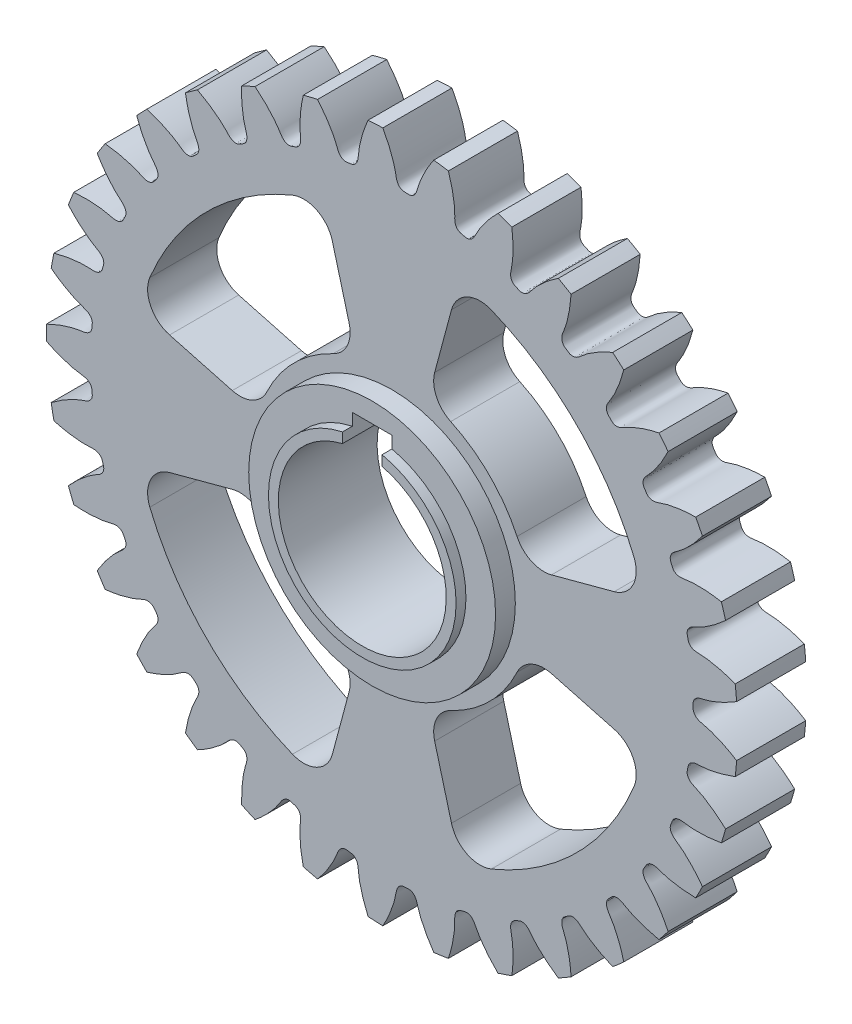
SolidWorks part; units mm, degrees
material "6061 合金"
ref_plane "前视基准面" through (0, 0, 0) normal (0, 0, 1) x (1, 0, 0)
ref_plane "上视基准面" through (0, 0, 0) normal (0, 1, 0) x (1, 0, 0)
ref_plane "右视基准面" through (0, 0, 0) normal (1, 0, 0) x (0, 0, -1)
ref_axis "基准轴1" through (0, 0, 55) along (0, 0, -1)
sketch "旋转草图小直齿轮" plane through (0, 0, 0) normal (1, 0, 0) x (0, 0, -1)
  line L0 (0, 0) -> (1, 0) construction
  line L1 (-10, 0) -> (-10, 35)
  line L2 (-10, 35) -> (10, 35)
  line L3 (10, 35) -> (10, 0)
  line L4 (10, 0) -> (-10, 0)
revolve "小直齿轮" add sketch "旋转草图小直齿轮" angle 360 about L0
sketch "齿草图小直齿轮" plane through (0, 0, 0) normal (0, 0, 1) x (1, 0, 0)
  arc A0 (35.0003, 2.644) -> (35.0003, -2.644) centre (0, 0) cw
  spline S0 degree 3 poles (35.0003, -2.644) (34.7907, -2.5117) (34.4792, -2.3248) (34.0654, -2.0965) (33.7742, -1.9447) (33.4951, -1.8076) (33.2285, -1.6843) (32.9751, -1.5743) (32.7352, -1.4768) (32.5093, -1.3912) (32.2979, -1.3168) (32.1012, -1.2527) (31.9198, -1.1983) (31.7538, -1.1528) (31.4805, -1.0842) (31.2197, -1.0388) (30.9914, -0.9382) (30.8888, -0.8816) (30.7862, -0.8086) (30.6834, -0.7107) (30.5866, -0.5765) (30.5189, -0.4083) (30.4921, -0.2094) (30.5043, 0) (30.4921, 0.2094) (30.5189, 0.4083) (30.5866, 0.5765) (30.6834, 0.7107) (30.7862, 0.8086) (30.8888, 0.8816) (30.9914, 0.9382) (31.2197, 1.0388) (31.4805, 1.0842) (31.7538, 1.1528) (31.9198, 1.1983) (32.1012, 1.2527) (32.2979, 1.3168) (32.5093, 1.3912) (32.7352, 1.4768) (32.9751, 1.5743) (33.2285, 1.6843) (33.4951, 1.8076) (33.7742, 1.9447) (34.0654, 2.0965) (34.4792, 2.3248) (34.7907, 2.5117) (35.0003, 2.644) knots 0 0 0 0 0.06742 0.098768 0.128542 0.15674 0.183364 0.208413 0.231887 0.253787 0.274112 0.292862 0.310037 0.325638 0.339663 0.38673 0.396938 0.407387 0.418555 0.431107 0.445833 0.463234 0.479825 0.5 0.520175 0.536766 0.554167 0.568893 0.581445 0.592613 0.603062 0.61327 0.660337 0.674362 0.689963 0.707138 0.725888 0.746213 0.768113 0.791587 0.816636 0.84326 0.871458 0.901232 0.93258 1 1 1 1
extrude "齿拉伸切除小直齿轮" cut sketch "齿草图小直齿轮" against normal blind 10 and the other way blind 10
pattern_circular "齿形小直齿轮" count 33 every 10.909 about axis through (0, 0, 55) along (0, 0, -1) of "齿拉伸切除小直齿轮"
sketch "孔旋转草图" plane through (0, 0, 0) normal (1, 0, 0) x (0, 0, -1)
  line L0 (0, 0) -> (1, 0) construction
  line L1 (-10, 0) -> (10, 0)
  line L2 (10, 0) -> (10, 5)
  line L3 (10, 5) -> (-10, 5)
  line L4 (-10, 5) -> (-10, 0)
  dimension "TaperSide1" = 5
  dimension "TaperSide2" = 5
revolve "孔旋转切除" cut sketch "孔旋转草图" angle 360 about L0
sketch "辅助草图小直齿轮" plane through (0, 0, 0) normal (0, 0, 1) x (1, 0, 0)
  circle A0 centre (0, 0) radius 33 construction
  circle A1 centre (0, 0) radius 31.0099 construction
  circle A2 centre (0, 0) radius 31.4316 construction
  circle A3 centre (0, 0) radius 35 construction
  circle A4 centre (0, 0) radius 30.5 construction
  dimension "PitchDiameter" = 66
  dimension "BaseDiameter" = 62.0197
  dimension "FormDiameter" = 62.8631
  dimension "MajorDiameter" = 70
  dimension "MinorDiameter" = 61
sketch "草图5" plane through (0, 0, 10) normal (0, 0, 1) x (1, 0, 0)
  circle A0 centre (0, 0) radius 40
  dimension "D1" = 80
extrude "切除-拉伸2" cut sketch "草图5" against normal blind 13
sketch "草图6" plane through (0, 0, -3) normal (0, 0, 1) x (1, 0, 0)
  line L1 (-2, 6.5) -> (2, 6.5)
  line L2 (-2, 6.5) -> (-2, 10.5)
  line L3 (-2, 10.5) -> (2, 10.5)
  line L4 (2, 6.5) -> (2, 10.5)
  line L5 (-2, 6.5) -> (2, 10.5) construction
  line L6 (-2, 10.5) -> (2, 6.5) construction
  circle A0 centre (0, 0) radius 8.5
  point P3 (0, 8.5)
  dimension "D1" = 17
  dimension "D2" = 4
  dimension "D3" = 4
extrude "切除-拉伸3" cut sketch "草图6" against normal blind 11 contours L4 A0 L2 L1 | L2 A0 L4 L1 | A0 L4 L3 L2 region at (0, 7.4618, -3) region at (0, -0.2614, -3) region at (0, 9.4592, -3)
sketch "草图7" plane through (0, 0, -3) normal (0, 0, 1) x (1, 0, 0)
  line L0 (-2, 8.2614) -> (-2, 10.5) construction
  line L1 (2, 8.2614) -> (2, 10.5) construction
  line L2 (-2, 10.5) -> (2, 10.5) construction
  line L3 (-2, 8.2614) -> (-2, 10.5)
  line L4 (2, 8.2614) -> (2, 10.5)
  line L5 (-2, 10.5) -> (2, 10.5)
  circle A1 centre (0, 0) radius 12.5
  arc A2 (-2, 8.2614) -> (2, 8.2614) centre (0, 0) ccw construction
  arc A3 (-2, 8.2614) -> (2, 8.2614) centre (0, 0) ccw
  dimension "D1" = 25
extrude "凸台-拉伸1" add sketch "草图7" along normal blind 2
sketch "草图8" plane through (0, 0, -1) normal (0, 0, 1) x (1, 0, 0)
  line L0 (2, 8.2614) -> (2, 10.5) construction
  line L1 (-2, 10.5) -> (-2, 8.2614) construction
  line L2 (2, 8.2614) -> (2, 9.2871)
  line L3 (-2, 9.2871) -> (-2, 8.2614)
  arc A0 (-2, 9.2871) -> (2, 9.2871) centre (0, 0) ccw
  arc A1 (-2, 8.2614) -> (2, 8.2614) centre (0, 0) ccw construction
  arc A2 (-2, 8.2614) -> (2, 8.2614) centre (0, 0) ccw
  dimension "D1" = 19
extrude "凸台-拉伸2" add sketch "草图8" along normal blind 1
sketch "草图9" plane through (0, 0, -3) normal (0, 0, 1) x (1, 0, 0)
  line L0 (0, 0) -> (0, 26.5) construction
  line L1 (3.6235, 13.523) -> (6.8587, 25.597)
  line L2 (13.523, 3.6235) -> (25.597, 6.8587)
  line L3 (13.523, -3.6235) -> (25.597, -6.8587)
  line L4 (3.6235, -13.523) -> (6.8587, -25.597)
  line L5 (-3.6235, -13.523) -> (-6.8587, -25.597)
  line L6 (-13.523, -3.6235) -> (-25.597, -6.8587)
  line L7 (-13.523, 3.6235) -> (-25.597, 6.8587)
  line L8 (-3.6235, 13.523) -> (-6.8587, 25.597)
  arc A0 (-6.8587, 25.597) -> (-25.597, 6.8587) centre (0, 0) ccw
  arc A1 (-3.6235, 13.523) -> (-13.523, 3.6235) centre (0, 0) ccw
  arc A2 (-25.597, -6.8587) -> (-6.8587, -25.597) centre (0, 0) ccw
  arc A3 (-13.523, -3.6235) -> (-3.6235, -13.523) centre (0, 0) ccw
  arc A4 (3.6235, -13.523) -> (13.523, -3.6235) centre (0, 0) ccw
  arc A5 (6.8587, -25.597) -> (25.597, -6.8587) centre (0, 0) ccw
  arc A6 (13.523, 3.6235) -> (3.6235, 13.523) centre (0, 0) ccw
  arc A7 (25.597, 6.8587) -> (6.8587, 25.597) centre (0, 0) ccw
  point P24 (0, 0)
  dimension "D1" = 53
  dimension "D2" = 28
  dimension "D3" = 15
  dimension "D4" = 60
  dimension "D5" = 4
extrude "切除-拉伸4" cut sketch "草图9" against normal through all
fillet "圆角1" radius 3 16 edges at (-25.597, 6.8587, -6.5) (-13.523, 3.6235, -6.5) (-3.6235, 13.523, -6.5) (-6.8587, 25.597, -6.5) (-13.523, -3.6235, -6.5) (-25.597, -6.8587, -6.5) (-6.8587, -25.597, -6.5) (-3.6235, -13.523, -6.5) (6.8587, -25.597, -6.5) (3.6235, -13.523, -6.5) (25.597, -6.8587, -6.5) (13.523, -3.6235, -6.5) (13.523, 3.6235, -6.5) (3.6235, 13.523, -6.5) (6.8587, 25.597, -6.5) (25.597, 6.8587, -6.5)
